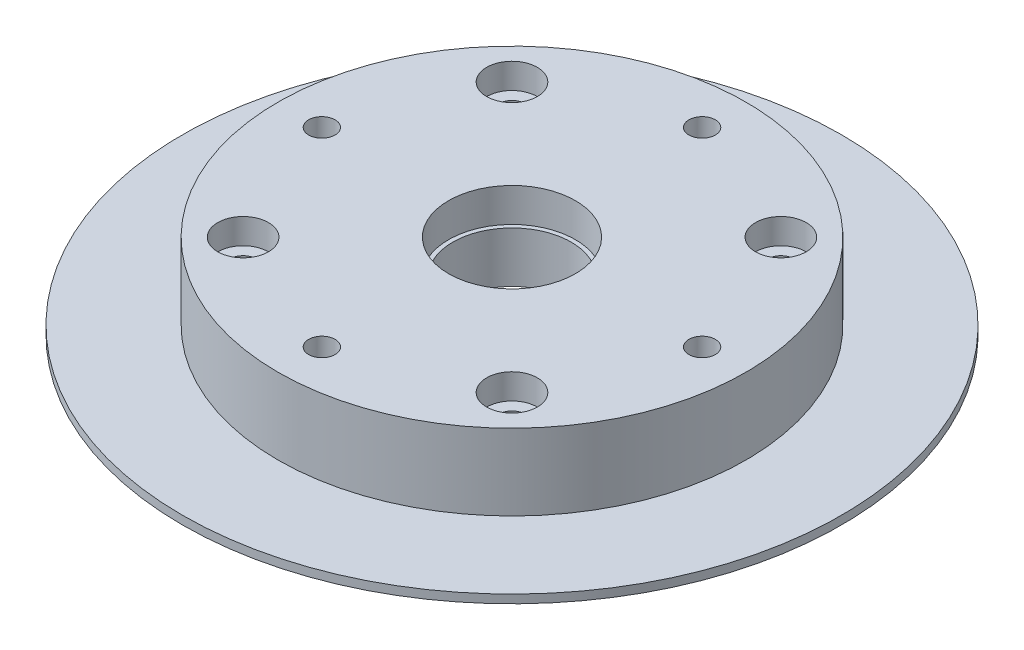
SolidWorks part; units mm, degrees
ref_plane "Front Plane" through (0, 0, 0) normal (0, 0, 1) x (1, 0, 0)
ref_plane "Top Plane" through (0, 0, 0) normal (0, 1, 0) x (1, 0, 0)
ref_plane "Right Plane" through (0, 0, 0) normal (1, 0, 0) x (0, 0, -1)
sketch "Sketch1" plane through (0, 0, 0) normal (0, 1, 0) x (1, 0, 0)
  line L0 (0, 0) -> (22.5, 0) construction
  circle A0 centre (0, 0) radius 39
  circle A1 centre (22.5, 0) radius 1.5635
  circle A2 centre (15.9099, -15.9099) radius 1.5635
  circle A3 centre (0, -22.5) radius 1.5635
  circle A4 centre (-15.9099, -15.9099) radius 1.5635
  circle A5 centre (-22.5, 0) radius 1.5635
  circle A6 centre (-15.9099, 15.9099) radius 1.5635
  circle A7 centre (0, 22.5) radius 1.5635
  circle A8 centre (15.9099, 15.9099) radius 1.5635
  circle A9 centre (0, 0) radius 7.5
  circle A10 centre (0, 0) radius 27.69
  circle A11 centre (0, 0) radius 7
  point P14 (0, 0)
  dimension "D2" = 78
  dimension "D3" = 15
  dimension "D5" = 3.127
  dimension "D6" = 55.38
  dimension "D7" = 14
  dimension "D4" = 22.5
  dimension "D1" = 8
extrude "Boss-Extrude1" add sketch "Sketch1" against normal blind 1 contours A0 A10 | A10 A2 A3 A4 A5 A6 A7 A8 A9 A1 region at (-37.8969, 0, 0) region at (-26.9068, 0, 0)
extrude "Boss-Extrude2" add sketch "Sketch1<3>" along normal blind 9 contours A10 A2 A3 A4 A5 A6 A7 A8 A9 A1 region at (-26.9068, 0, 0)
sketch "Sketch1<3>" plane through (0, 0, 0) normal (0, 1, 0) x (1, 0, 0) same geometry as "Sketch1"
sketch "Sketch2" plane through (0, 9, 0) normal (0, 1, 0) x (1, 0, 0)
  circle A0 centre (15.9099, 15.9099) radius 3
  circle A1 centre (15.9099, -15.9099) radius 3
  circle A2 centre (-15.9099, -15.9099) radius 3
  circle A3 centre (-15.9099, 15.9099) radius 3
  point P12 (0, 0)
  circle M4 centre (-15.9099, -15.9099) radius 1.5635
  circle M6 centre (-15.9099, 15.9099) radius 1.5635
  circle M8 centre (15.9099, 15.9099) radius 1.5635
  dimension "D1" = 6
  dimension "D2" = 4
extrude "Cut-Extrude1" cut sketch "Sketch2" against normal blind 3 contours A3 M6 | A0 M8 | A2 M4 | A1 region at (12.9948, 9, -15.9099) region at (-18.825, 9, 15.9099) region at (-18.825, 9, -15.9099)
extrude "Boss-Extrude3" add sketch "Sketch1<4>" against normal blind 1 contours A11 A9 region at (-7.2879, 0, 0)
sketch "Sketch1<4>" plane through (0, 0, 0) normal (0, 1, 0) x (1, 0, 0) same geometry as "Sketch1"
extrude "Boss-Extrude4" add sketch "Sketch1<5>" along normal blind 5 contours A11 A9 region at (-7.2879, 0, 0)
sketch "Sketch1<5>" plane through (0, 0, 0) normal (0, 1, 0) x (1, 0, 0) same geometry as "Sketch1"
sketch "Sketch3" plane through (0, -1, 0) normal (0, -1, 0) x (1, 0, 0)
  circle A0 centre (22.5, 0) radius 1.925
  circle A1 centre (0, -22.5) radius 1.925
  circle A2 centre (-22.5, 0) radius 1.925
  circle A3 centre (0, 22.5) radius 1.925
  point P12 (0, 0)
  dimension "D1" = 3.85
  dimension "D2" = 4
extrude "Cut-Extrude2" cut sketch "Sketch3" against normal blind 4
equation "\"bearing_21_OD\"= 21mm"
equation "\"pin_cirlce_diameter\"= 75mm"
equation "\"pin_diam\"= 6mm"
equation "\"gear_thickness\"= 4mm"
equation "\"ball_bearing_diam\"= 2.96mm"
equation "\"bearing_21_outer_clearance\"= 0.127mm'change this"
equation "\"bearing_15_OD\"= 15mm"
equation "\"bearing_15_outer_clearance\"= 0mm'change this"
equation "\"thrust_bearing_thickness\"= 5mm'measure this irl and change"
equation "\"D3@Sketch1\"=\"bearing_15_OD\""
equation "\"D1@Boss-Extrude2\"=\"thrust_bearing_thickness\"+4mm"
equation "\"D1@Boss-Extrude4\"=\"thrust_bearing_thickness\""
